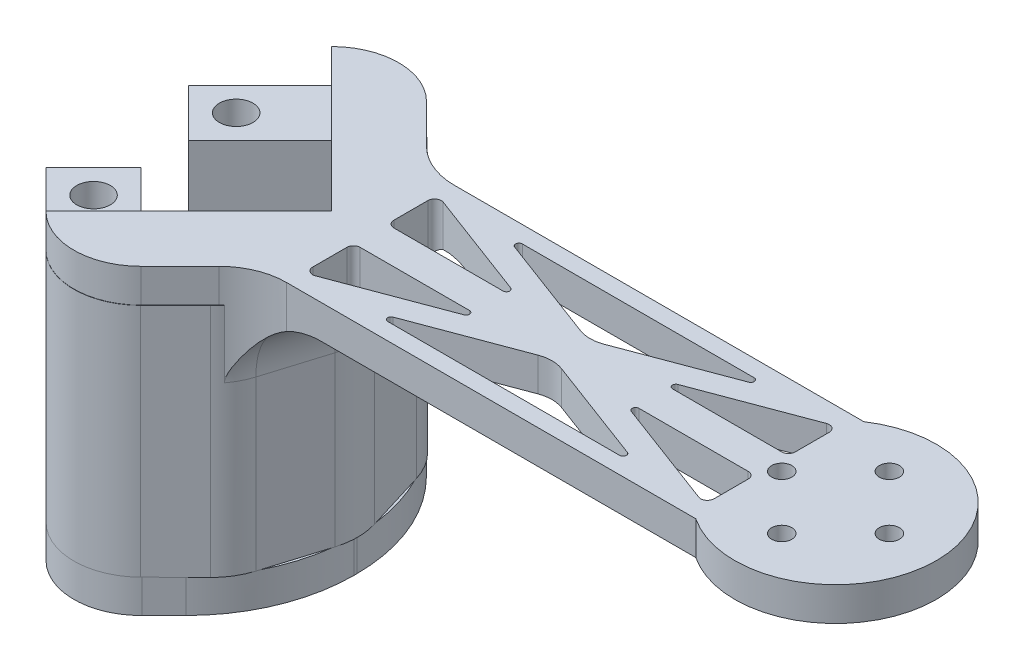
SolidWorks part; units mm, degrees
ref_plane "Front Plane" through (0, 0, 0) normal (0, 0, 1) x (1, 0, 0)
ref_plane "Top Plane" through (0, 0, 0) normal (0, 1, 0) x (1, 0, 0)
ref_plane "Right Plane" through (0, 0, 0) normal (1, 0, 0) x (0, 0, -1)
sketch "Sketch1" plane through (0, 0, 0) normal (0, 1, 0) x (1, 0, 0)
  line L0 (0, 0) -> (75, 0) construction
  line L1 (0, 0) -> (-21.2132, -21.2132) construction
  line L2 (0, 0) -> (-21.2132, 21.2132) construction
  line L3 (-21.2132, 21.2132) -> (-14.1314, 28.295) construction
  line L4 (-21.2132, -21.2132) -> (-14.1206, -28.3058) construction
  line L5 (0, -12.5) -> (0, 12.5) construction
  line L6 (0, 12.5) -> (66.7084, 12.5) construction
  line L7 (0, -12.5) -> (66.7084, -12.5) construction
  line L8 (-7.0496, -21.2347) -> (-1.2438, -15.4289)
  line L9 (-7.0603, 21.224) -> (-1.2653, 15.4289)
  line L10 (-21.2025, 21.224) -> (-21.2132, 21.2132)
  line L11 (-21.2132, 21.2132) -> (0, 0)
  line L12 (0, 0) -> (-21.2132, -21.2132)
  line L13 (-21.2132, -21.2132) -> (-21.1917, -21.2347)
  line L14 (5.8058, 12.5) -> (66.7084, 12.5)
  line L15 (5.8273, -12.5) -> (66.7084, -12.5)
  circle A0 centre (75, 0) radius 8 construction
  circle A1 centre (75, 0) radius 15 construction
  arc A2 (66.7084, 12.5) -> (66.7084, -12.5) centre (75, 0) cw
  arc A3 (-1.2653, 15.4289) -> (5.8058, 12.5) centre (5.8058, 22.5) ccw
  arc A4 (-1.2438, -15.4289) -> (5.8273, -12.5) centre (5.8273, -22.5) cw
  arc A5 (-21.1917, -21.2347) -> (-7.0496, -21.2347) centre (-14.1206, -14.1636) ccw
  arc A6 (-21.2025, 21.224) -> (-7.0603, 21.224) centre (-14.1314, 14.1529) cw
  circle A7 centre (67, 0) radius 1.5
  circle A8 centre (75, 8) radius 1.5
  circle A9 centre (83, 0) radius 1.5
  circle A10 centre (75, -8) radius 1.5
  point P5 (67, 0)
  point P6 (75, 8)
  point P7 (83, 0)
  point P8 (75, -8)
  point P19 (1.6636, 12.5)
  point P21 (0, 0)
  point P25 (1.6851, -12.5)
  dimension "D1" = 10
extrude "Boss-Extrude1" add sketch "Sketch1" along normal blind 5 contours A6 L10 L11 L12 L13 A5 L8 A4 L15 A2 L14 A3 L9 A10 A9 A8 A7 region at (35.3094, 0, 0.0025)
sketch "Sketch2" plane through (0, 5, 0) normal (0, 1, 0) x (1, 0, 0)
  line L0 (-1000, 0) -> (49000, 0) construction
  line L1 (5.8058, -987.5) -> (5.8058, 49012.5) construction
  line L2 (65.5, -1000) -> (65.5, 49000) construction
  line L3 (5.8058, 12.5) -> (66.7084, 12.5) construction
  line L4 (5.8058, 12.5) -> (5.8058, 10) construction
  line L5 (5.8058, 0) -> (5.8058, 2.5) construction
  line L6 (-994.1942, 10) -> (49005.8058, 10) construction
  line L7 (-994.1942, 2.5) -> (49005.8058, 2.5) construction
  line L8 (5.8058, 2.5) -> (65.5, 2.5) construction
  line L9 (5.8058, 2.5) -> (25.8058, 2.5) construction
  line L10 (65.5, 2.5) -> (45.5, 2.5) construction
  line L11 (35.6529, 10) -> (55.6529, 10) construction
  line L12 (35.6529, 10) -> (15.6529, 10) construction
  line L13 (5.8058, 8.557) -> (5.8058, 3.5)
  line L14 (6.8058, 2.5) -> (23.0484, 2.5)
  line L15 (23.224, 3.4682) -> (7.1569, 9.4933)
  line L16 (18.4102, 10) -> (52.8956, 10)
  line L17 (53.0711, 9.0318) -> (37.4085, 3.1584)
  line L18 (33.8973, 3.1584) -> (18.2347, 9.0318)
  line L19 (48.0818, 3.4682) -> (64.1489, 9.4933)
  line L20 (65.5, 8.557) -> (65.5, 3.5)
  line L21 (64.5, 2.5) -> (48.2573, 2.5)
  line L22 (65.5, -8.557) -> (65.5, -3.5)
  line L23 (48.0818, -3.4682) -> (64.1489, -9.4933)
  line L24 (64.5, -2.5) -> (48.2573, -2.5)
  line L25 (53.0711, -9.0318) -> (37.4085, -3.1584)
  line L26 (18.4102, -10) -> (52.8956, -10)
  line L27 (33.8973, -3.1584) -> (18.2347, -9.0318)
  line L28 (6.8058, -2.5) -> (23.0484, -2.5)
  line L29 (5.8058, -8.557) -> (5.8058, -3.5)
  line L30 (23.224, -3.4682) -> (7.1569, -9.4933)
  arc A0 (7.1569, 9.4933) -> (5.8058, 8.557) centre (6.8058, 8.557) ccw
  arc A1 (64.5, 2.5) -> (65.5, 3.5) centre (64.5, 3.5) ccw
  arc A2 (65.5, 8.557) -> (64.1489, 9.4933) centre (64.5, 8.557) ccw
  arc A3 (5.8058, 3.5) -> (6.8058, 2.5) centre (6.8058, 3.5) ccw
  arc A4 (37.4085, 3.1584) -> (33.8973, 3.1584) centre (35.6529, 7.84) cw
  arc A5 (48.2573, 2.5) -> (48.0818, 3.4682) centre (48.2573, 3) cw
  arc A6 (53.0711, 9.0318) -> (52.8956, 10) centre (52.8956, 9.5) ccw
  arc A7 (18.2347, 9.0318) -> (18.4102, 10) centre (18.4102, 9.5) cw
  arc A8 (23.224, 3.4682) -> (23.0484, 2.5) centre (23.0484, 3) cw
  arc A9 (65.5, -8.557) -> (64.1489, -9.4933) centre (64.5, -8.557) cw
  arc A10 (64.5, -2.5) -> (65.5, -3.5) centre (64.5, -3.5) cw
  arc A11 (48.2573, -2.5) -> (48.0818, -3.4682) centre (48.2573, -3) ccw
  arc A12 (53.0711, -9.0318) -> (52.8956, -10) centre (52.8956, -9.5) cw
  arc A13 (37.4085, -3.1584) -> (33.8973, -3.1584) centre (35.6529, -7.84) ccw
  arc A14 (18.2347, -9.0318) -> (18.4102, -10) centre (18.4102, -9.5) ccw
  arc A15 (5.8058, -3.5) -> (6.8058, -2.5) centre (6.8058, -3.5) cw
  arc A16 (7.1569, -9.4933) -> (5.8058, -8.557) centre (6.8058, -8.557) cw
  arc A17 (23.224, -3.4682) -> (23.0484, -2.5) centre (23.0484, -3) ccw
  point P14 (65.5, 10)
  point P19 (65.5, 2.5)
  point P20 (35.6529, 2.5)
  point P37 (65.5, 10)
  point P43 (35.6529, 2.5)
  dimension "D3" = 1
  dimension "D4" = 5
  dimension "D5" = 0.5
  dimension "D1" = 59.6942
  dimension "D2" = 12.5
extrude "Cut-Extrude2" cut sketch "Sketch2" against normal blind 5
sketch "Sketch3" plane through (0, 0, 0) normal (0, -1, 0) x (1, 0, 0)
  line L0 (0, 0) -> (-14.1421, -14.1421) construction
  line L1 (-21.2132, -21.2132) -> (0, 0) construction
  line L2 (0, 0) -> (-14.1421, 14.1421) construction
  line L3 (0, 0) -> (-21.2132, 21.2132) construction
  line L4 (-14.1421, -14.1421) -> (0, 0)
  line L5 (-14.1421, -14.1421) -> (-21.2132, -7.0711)
  line L6 (0, 0) -> (-14.1421, 14.1421)
  line L7 (-21.2132, 7.0711) -> (-14.1421, 14.1421)
  line L8 (-21.1917, 21.2347) -> (-21.1552, 21.2712)
  line L9 (-7.0715, 21.3293) -> (-1.8046, 16.1484)
  line L10 (0.7427, 11.9534) -> (3.5104, 2.9356)
  line L11 (3.5095, -2.9354) -> (0.7421, -11.9426)
  line L12 (-21.1917, 21.2347) -> (-31.8198, 10.6066)
  line L13 (-31.8198, -10.6066) -> (-21.159, -21.2674)
  line L14 (-7.0715, -21.3215) -> (-1.8004, -16.1309)
  line L15 (-31.8198, 10.6066) -> (-31.8198, -10.6066)
  line L16 (-728.32, -700.0357) -> (34627.0191, 34655.3033) construction
  line L17 (-728.32, 700.0357) -> (34627.0191, -34655.3033) construction
  line L18 (-21.2132, 7.0711) -> (-28.2843, 0)
  line L19 (-28.2843, 0) -> (-21.2132, -7.0711)
  arc A1 (-1.2438, 15.4289) -> (5.8273, 12.5) centre (5.8273, 22.5) ccw construction
  arc A2 (5.8058, -12.5) -> (-1.2653, -15.4289) centre (5.8058, -22.5) ccw construction
  arc A3 (3.5104, 2.9356) -> (3.5095, -2.9354) centre (-6.0495, 0.0016) cw
  arc A4 (-1.8046, 16.1484) -> (0.7427, 11.9534) centre (-8.8172, 9.0193) cw
  arc A5 (0.7421, -11.9426) -> (-1.8004, -16.1309) centre (-8.8169, -9.0057) cw
  arc A6 (-21.159, -21.2674) -> (-7.0715, -21.3215) centre (-14.088, -14.1963) ccw
  arc A7 (-21.1552, 21.2712) -> (-7.0715, 21.3293) centre (-14.0841, 14.2002) cw
  point P10 (-28.2843, 0)
  point P24 (-42.4264, 0)
  point P31 (0, 14.3733)
  point P34 (0, -14.3579)
  dimension "D2" = 10
extrude "Boss-Extrude2" add sketch "Sketch3" along normal blind 35 contours L14 A5 L11 A3 L10 A4 L9 A7 L8 L12 L15 L13 A6 | L4 L6 L7 L18 L19 L5
sketch "Sketch4" plane through (0, -35, 0) normal (0, -1, 0) x (1, 0, 0)
  line L0 (0, 0) -> (-17.6777, -17.6777) construction
  line L1 (0, 0) -> (-17.6777, 17.6777) construction
  line L2 (-17.6777, -17.6777) -> (-24.7487, -10.6066) construction
  line L3 (-17.6777, 17.6777) -> (-24.7487, 10.6066) construction
  circle A0 centre (-24.7487, 10.6066) radius 2.5
  circle A1 centre (-24.7487, -10.6066) radius 2.5
extrude "Cut-Extrude3" cut sketch "Sketch4" against normal through all both and the other way through all
sketch "Sketch5" plane through (0, -35, 0) normal (0, -1, 0) x (1, 0, 0)
  line L0 (0, 0) -> (-21.1552, 21.2712)
  line L1 (0, 0) -> (-21.159, -21.2674)
  line L2 (-7.0169, -21.159) -> (-3.7307, -17.8729)
  line L3 (-7.013, 21.1552) -> (-3.7307, 17.8728)
  line L4 (3.5917, 0.1905) -> (3.5916, -0.1998)
  arc A0 (-21.1552, 21.2712) -> (-7.013, 21.1552) centre (-14.1421, 14.1421) cw
  arc A1 (-21.159, -21.2674) -> (-7.0169, -21.159) centre (-14.1421, -14.1421) ccw
  arc A2 (-3.7307, -17.8729) -> (3.5916, -0.1998) centre (-21.4084, -0.1952) ccw
  arc A3 (-3.7307, 17.8728) -> (3.5917, 0.1905) centre (-21.4083, 0.1951) cw
  dimension "D1" = 25
extrude "Boss-Extrude3" add sketch "Sketch5" along normal blind 5
fillet "Fillet1" radius 10 4 edges at (2.1258, 0, -7.439) (2.1265, 0, 7.4445) (3.5095, -17.5, -2.9354) (3.5104, -17.5, 2.9356) type face fillet first side face at (3.7302, -17.5, 0.0001) first side face at (35.6529, 0, -7.3681) second side face at (2.129, -23.3333, 7.4365) second side face at (2.127, -23.3333, -7.435)
sketch "Sketch6" plane through (0, -35, 0) normal (0, -1, 0) x (1, 0, 0)
  line L0 (-31.8198, -10.6066) -> (-24.7487, -3.5355)
  line L1 (-14.1421, -14.1421) -> (-28.2843, 0) construction
  line L2 (-31.8198, 10.6066) -> (-24.7487, 3.5355)
  line L3 (-14.1421, 14.1421) -> (-28.2843, 0) construction
  line L4 (-31.8198, 10.6066) -> (-31.8198, -10.6066)
  line L5 (-24.7487, -3.5355) -> (-28.2843, 0)
  line L6 (-28.2843, 0) -> (-24.7487, 3.5355)
extrude "Cut-Extrude4" cut sketch "Sketch6" against normal through all both and the other way through all
